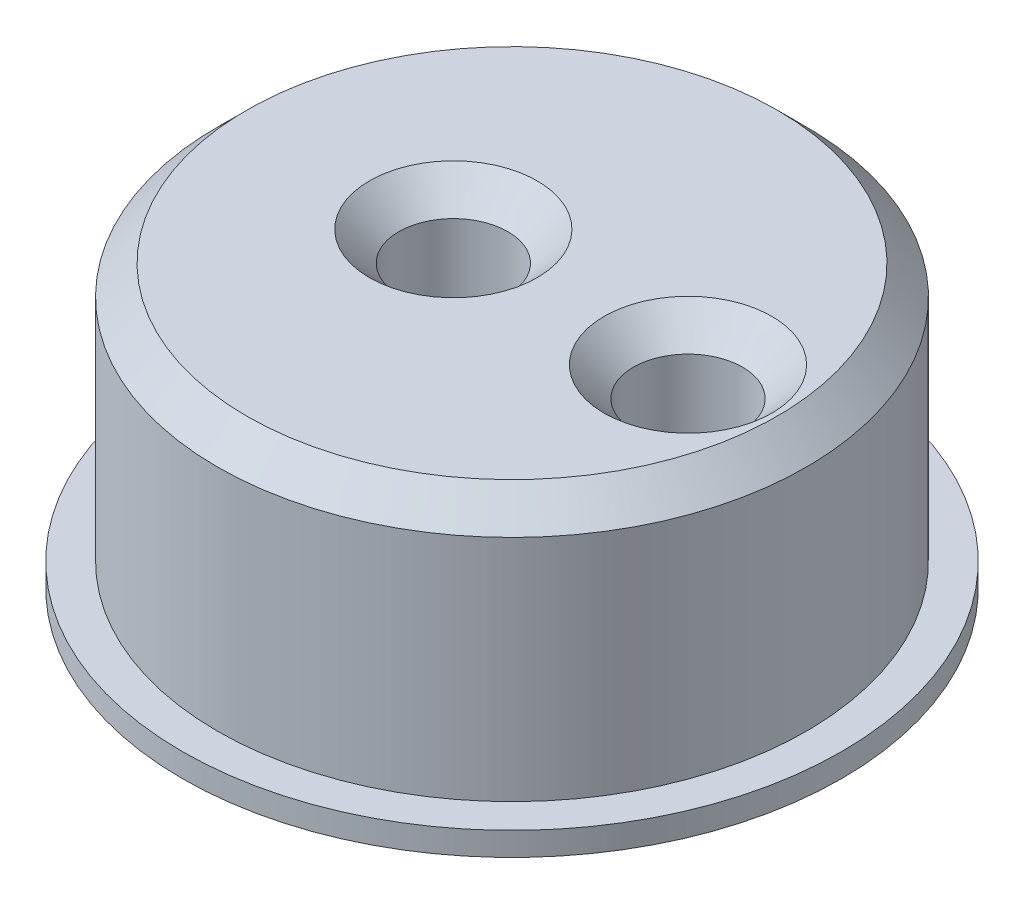
SolidWorks part; units mm, degrees
ref_plane "前视基准面" through (0, 0, 0) normal (0, 0, 1) x (1, 0, 0)
ref_plane "上视基准面" through (0, 0, 0) normal (0, 1, 0) x (1, 0, 0)
ref_plane "右视基准面" through (0, 0, 0) normal (1, 0, 0) x (0, 0, -1)
other "Configuration Table"
sketch "草图1" plane through (0, 0, 0) normal (0, 1, 0) x (1, 0, 0)
  line L0 (1, 6.4178) -> (1, -6.4114) construction
  line L1 (-5.7349, 0) -> (5.8104, 0) construction
  circle A0 centre (0, 0) radius 5.02
  circle A1 centre (3, 0) radius 0.93
  circle A2 centre (-1, 0) radius 0.93
  dimension "D1" = 10.04
  dimension "D3" = 4
  dimension "D4" = 1.86
  dimension "D2" = 1
extrude "凸台-拉伸1" add sketch "草图1" along normal blind 4.4
sketch "草图3" plane through (0, 0, 0) normal (0, -1, 0) x (1, 0, 0)
  circle A0 centre (3, 0) radius 0.93 construction
  circle A1 centre (0, 0) radius 5.02 construction
  circle A3 centre (-1, 0) radius 0.93 construction
  circle A4 centre (3, 0) radius 0.93
  circle A5 centre (-1, 0) radius 0.93
  circle A6 centre (0, 0) radius 5.02 construction
  circle A7 centre (0, 0) radius 5.62
  dimension "D1" = 0.6
extrude "凸台-拉伸2" add sketch "草图3" along normal blind 0.4
chamfer "倒角1" distance 0.5 angle 45 5 edges at (0, 4.4, 5.02) (-1, 4.4, -0.93) (3, 4.4, 0.93) (-1, -0.4, -0.93) (3, -0.4, -0.93)
ref_axis "基准轴1" through (0, 3.9, 0) along (0, -1, 0)
sketch "草图2" plane through (0, 0, 0) normal (0, 1, 0) x (1, 0, 0)
  line L0 (-5.9042, 0) -> (6.2358, 0) construction
